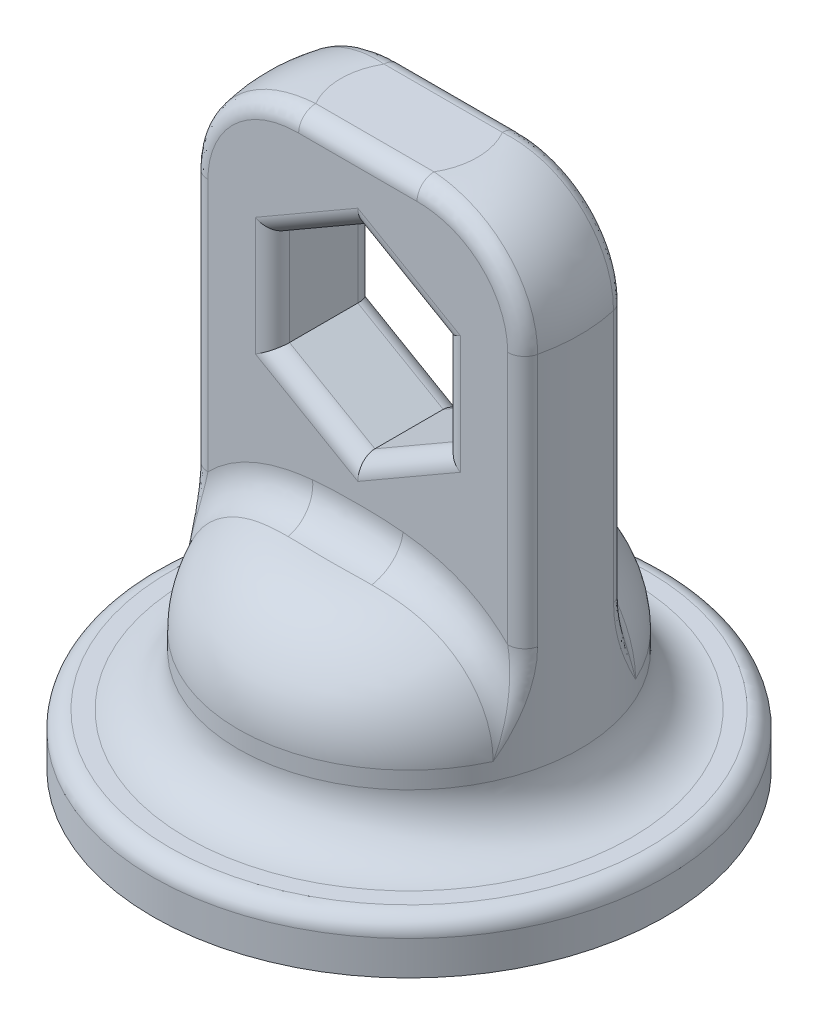
SolidWorks part; units mm, degrees
ref_plane "前视基准面" through (0, 0, 0) normal (0, 0, 1) x (1, 0, 0)
ref_plane "上视基准面" through (0, 0, 0) normal (0, 1, 0) x (1, 0, 0)
ref_plane "右视基准面" through (0, 0, 0) normal (1, 0, 0) x (0, 0, -1)
other "Configuration Table"
sketch "草图1" plane through (0, 0, 0) normal (0, 1, 0) x (1, 0, 0)
  circle A0 centre (0, 0) radius 15
  dimension "D1" = 30
extrude "凸台-拉伸1" add sketch "草图1" along normal blind 3
sketch "草图2" plane through (0, 3, 0) normal (0, 1, 0) x (1, 0, 0)
  circle A0 centre (0, 0) radius 10
  dimension "D1" = 20
extrude "凸台-拉伸2" add sketch "草图2" along normal blind 30
sketch "草图4" plane through (0, 33, 0) normal (0, 1, 0) x (1, 0, 0)
  line L1 (-11.3932, 3) -> (12.6263, 3)
  line L2 (-11.3932, 3) -> (-11.3932, -3)
  line L3 (-11.3932, -3) -> (12.6263, -3)
  line L4 (12.6263, 3) -> (12.6263, -3)
  dimension "D1" = 3
  dimension "D2" = 3
extrude "切除-拉伸1" cut sketch "草图4" against normal blind 20 flip side to cut
sketch "草图5" plane through (0, 0, -3) normal (0, 0, -1) x (-1, 0, 0)
  line L0 (-9.5394, 33) -> (9.5394, 33) construction
  line L1 (5, 20.1132) -> (5, 25.8868)
  line L2 (5, 25.8868) -> (0, 28.7735)
  line L3 (0, 28.7735) -> (-5, 25.8868)
  line L4 (-5, 25.8868) -> (-5, 20.1132)
  line L5 (-5, 20.1132) -> (0, 17.2265)
  line L6 (0, 17.2265) -> (5, 20.1132)
  circle A0 centre (0, 23) radius 5 construction
  point P11 (0, 33)
  dimension "D1" = 10
  dimension "D2" = 0
  dimension "D3" = 10
  dimension "D4" = 0
extrude "切除-拉伸3" cut sketch "草图5" against normal blind 20
fillet "圆角1" radius 3 1 edges at (0, 3, 10)
fillet "圆角2" radius 6 2 edges at (0, 13, -10) (0, 13, 10)
fillet "圆角3" radius 2 6 edges at (8.2768, 10.5951, -3) (-7.4863, 11.4131, -3) (-8.2768, 10.5951, 3) (7.4863, 11.4131, 3) (0, 13, -3) (0, 13, 3)
fillet "圆角4" radius 6 2 edges at (10, 33, 0) (-10, 33, 0)
fillet "圆角5" radius 1 26 edges at (9.4422, 9.2618, -3.2932) (-9.4422, 9.2618, -3.2932) (9.4422, 9.2618, 3.2932) (-9.4422, 9.2618, 3.2932) (-5, 23, -3) (-2.5, 27.3301, -3) (2.5, 27.3301, -3) (5, 23, -3) (2.5, 18.6699, -3) (-2.5, 18.6699, -3) (-8.2768, 30.5951, -3) (-9.5394, 19.1309, -3) (9.5394, 19.1309, -3) (7.4863, 31.4131, -3) (0, 33, -3) (2.5, 18.6699, 3) (5, 23, 3) (2.5, 27.3301, 3) (-2.5, 27.3301, 3) (-5, 23, 3) (-2.5, 18.6699, 3) (-9.5394, 19.1309, 3) (-7.4863, 31.4131, 3) (0, 33, 3) (8.2768, 30.5951, 3) (9.5394, 19.1309, 3)
fillet "圆角6" radius 1 1 edges at (0, 3, 15)
